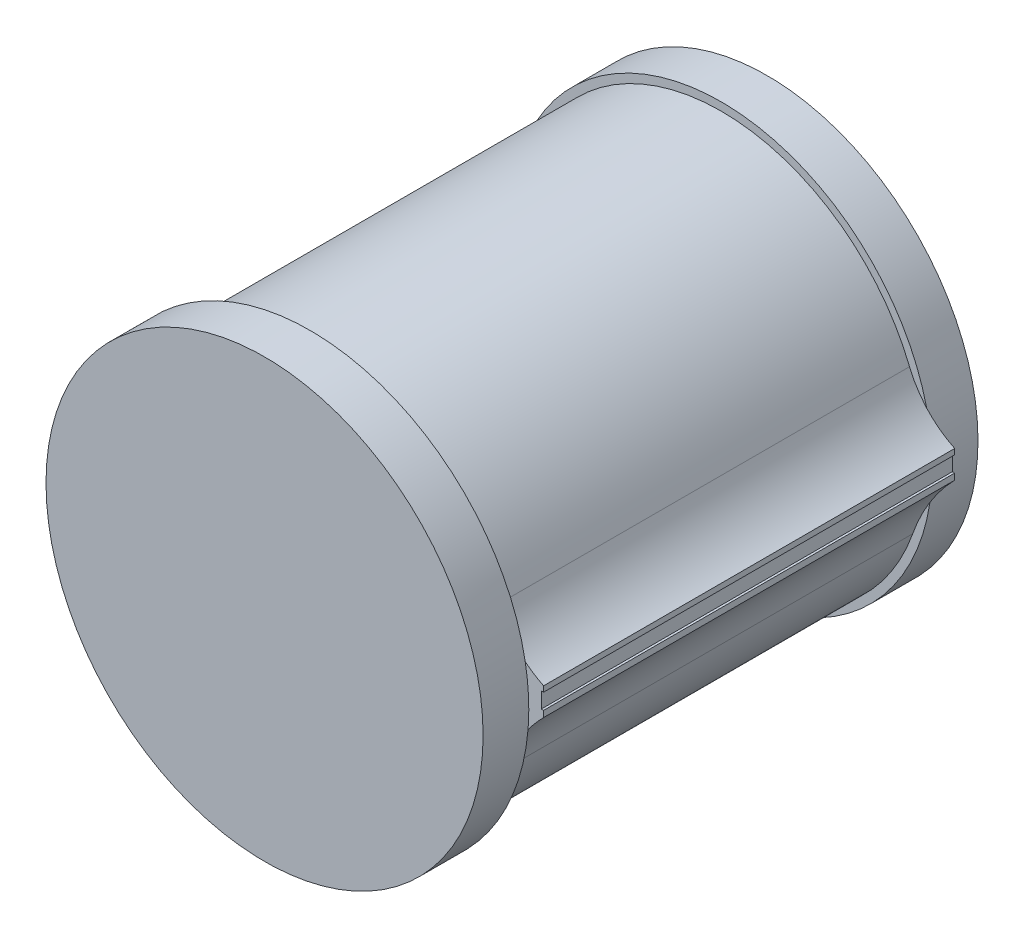
SolidWorks part; units mm, degrees
ref_plane "Alzado" through (0, 0, 0) normal (0, 0, 1) x (1, 0, 0)
ref_plane "Planta" through (0, 0, 0) normal (0, 1, 0) x (1, 0, 0)
ref_plane "Vista lateral" through (0, 0, 0) normal (1, 0, 0) x (0, 0, -1)
sketch "Croquis1" plane through (0, 9.52, 0) normal (0, 0, 1) x (1, 0, 0)
  circle A0 centre (-87.8842, 0) radius 44.4223
extrude "Saliente-Extruir1" add sketch "Croquis1" along normal mid plane 100
sketch "Croquis2" plane through (0, 9.52, -50) normal (0, 0, -1) x (-1, 0, 0)
  circle A0 centre (87.8842, 0) radius 46.1996
extrude "Saliente-Extruir2" add sketch "Croquis2" along normal blind 10
sketch "Croquis3" plane through (0, 9.52, 50) normal (0, 0, 1) x (1, 0, 0)
  circle A0 centre (-87.8842, 0) radius 47.8487
extrude "Saliente-Extruir3" add sketch "Croquis3" against normal blind 10
sketch "Croquis5" plane through (0, 9.52, -60) normal (0, 0, -1) x (-1, 0, 0)
  circle A0 centre (87.8842, 0) radius 40.5182
extrude "Cortar-Extruir4" cut sketch "Croquis5" against normal blind 105
sketch "Croquis8" plane through (0, 0, 0) normal (1, 0, 0) x (0, 0, -1)
  line L0 (50, 15.5424) -> (-40, 15.5424)
  line L1 (50, 53.9424) -> (50, -34.9023) construction
  line L2 (-40, -34.9023) -> (-40, 53.9424) construction
  line L3 (-40, 15.5424) -> (-40, 9.52)
  line L4 (-40, -38.3287) -> (-40, 57.3687) construction
  line L5 (-40, 9.52) -> (50, 9.52)
  line L6 (50, 9.52) -> (50, 15.5424)
extrude "Saliente-Extruir4" add sketch "Croquis8" against normal mid plane 91
sketch "Croquis9" plane through (0, 15.5424, 0) normal (0, 1, 0) x (1, 0, 0)
  line L0 (-13.9656, -40) -> (-13.9656, 50)
  line L1 (-40.416, -40) -> (45.5, -40) construction
  line L2 (-42.0788, 50) -> (45.5, 50) construction
  line L3 (-13.9656, 50) -> (45.5, 50)
  line L4 (45.5, 50) -> (45.5, -40)
  line L5 (45.5, -40) -> (-13.9656, -40)
extrude "Cortar-Extruir5" cut sketch "Croquis9" against normal blind 45
sketch "Croquis10" plane through (0, 15.5424, 0) normal (0, 1, 0) x (1, 0, 0)
  line L0 (-42.0788, 50) -> (-13.9656, 50) construction
  line L1 (-13.9656, -40) -> (-36.7878, -40)
  line L2 (-13.9656, -40) -> (-13.9656, 50)
  line L3 (-13.9656, 50) -> (-36.7878, 50)
  line L4 (-36.7878, -40) -> (-36.7878, 50)
extrude "Cortar-Extruir6" cut sketch "Croquis10" against normal blind 45
sketch "Croquis11" plane through (-36.7878, 0, 0) normal (1, 0, 0) x (0, 0, -1)
  line L0 (-40, 9.52) -> (-40, 15.5424) construction
  line L1 (-40, 10.884) -> (50, 10.884)
  line L2 (-40, 10.884) -> (-40, 14.3311)
  line L3 (-40, 14.3311) -> (50, 14.3311)
  line L4 (50, 10.884) -> (50, 14.3311)
  line L5 (50, 9.52) -> (50, 15.5424) construction
extrude "Cortar-Extruir7" cut sketch "Croquis11" against normal blind 0.5
fillet "Redondeo1" radius 20 1 edges at (-43.872, 15.5424, -5)
fillet "Redondeo2" radius 40 1 edges at (-43.4619, 9.52, -5)
